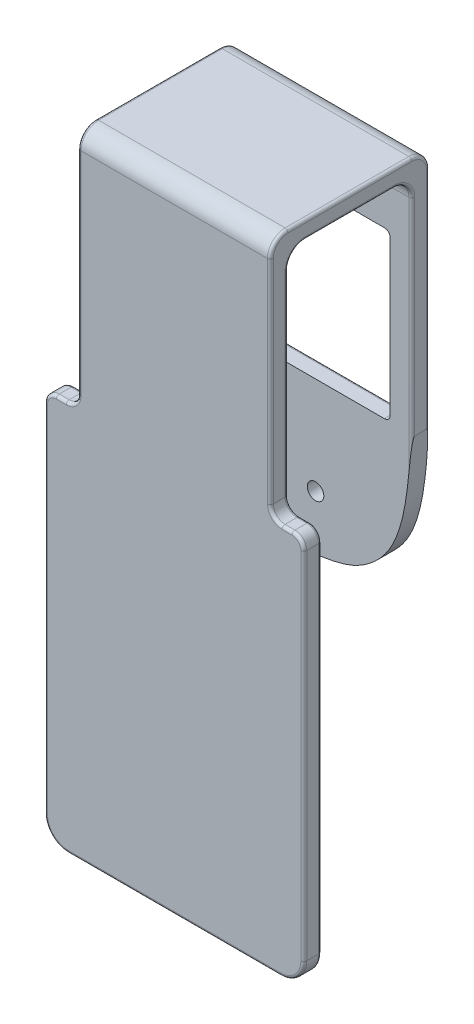
SolidWorks part; units mm, degrees
material "Plastique personnalisé"
ref_plane "Plan de face" through (0, 0, 0) normal (0, 0, 1) x (1, 0, 0)
ref_plane "Plan de dessus" through (0, 0, 0) normal (0, 1, 0) x (1, 0, 0)
ref_plane "Plan de droite" through (0, 0, 0) normal (1, 0, 0) x (0, 0, -1)
sketch "Esquisse1" plane through (0, 0, 0) normal (0, 0, 1) x (1, 0, 0)
  line L0 (19.7337, 104.7956) -> (19.7337, 0) construction
  line L1 (0, 0) -> (44, 0)
  line L2 (0, 0) -> (0, 108)
  line L3 (0, 108) -> (44, 108)
  line L4 (44, 0) -> (44, 108)
  dimension "D1" = 108
  dimension "D2" = 44
extrude "Boss.-Extru.1" add sketch "Esquisse1" along normal blind 3
sketch "Esquisse5" plane through (0, 0, 0) normal (0, 0, -1) x (-1, 0, 0)
  line L0 (-22, 108) -> (-22, 0) construction
  line L1 (-44, 108) -> (0, 108) construction
  line L2 (0, 0) -> (-44, 0) construction
ref_axis "Axe4" through (22, 108, 0) along (0, -1, 0)
fillet "Congé1" radius 4 2 edges at (44, 0, 1.5) (0, 0, 1.5)
ref_plane "Plan1" through (0, 0, -21) normal (0, 0, 1) x (1, 0, 0)
sketch "Esquisse6" plane through (0, 0, -21) normal (0, 0, 1) x (1, 0, 0)
  line L0 (44, 4) -> (44, 108) construction
  line L1 (0, 108) -> (44, 108)
  line L2 (0, 108) -> (0, 41)
  line L3 (0, 41) -> (44, 41)
  line L4 (44, 108) -> (44, 41)
  dimension "D1" = 67
extrude "Boss.-Extru.2" add sketch "Esquisse6" against normal blind 3 separate body
sketch "Esquisse7" plane through (0, 0, -24) normal (0, 0, -1) x (-1, 0, 0)
  circle A0 centre (-21.9933, 50.2726) radius 1.4
  dimension "D1" = 2.8
sketch "Esquisse8" plane through (0, 0, -24) normal (0, 0, -1) x (-1, 0, 0)
  line L1 (-33.6631, 94.8338) -> (-9.59, 94.8338)
  line L2 (-34.6631, 93.8338) -> (-34.6631, 67.778)
  line L3 (-33.6631, 66.778) -> (-9.59, 66.778)
  line L4 (-8.59, 93.8338) -> (-8.59, 67.778)
  arc A0 (-34.6631, 67.778) -> (-33.6631, 66.778) centre (-33.6631, 67.778) ccw
  arc A1 (-9.59, 66.778) -> (-8.59, 67.778) centre (-9.59, 67.778) ccw
  arc A2 (-9.59, 94.8338) -> (-8.59, 93.8338) centre (-9.59, 93.8338) cw
  arc A3 (-33.6631, 94.8338) -> (-34.6631, 93.8338) centre (-33.6631, 93.8338) ccw
  dimension "D1" = 1
extrude "Enlèv. mat.-Extru.1" cut sketch "Esquisse8" against normal blind 3
extrude "Enlèv. mat.-Extru.2" cut sketch "Esquisse7" against normal blind 3
fillet "Congé3" radius 0.5 8 edges at (21.6266, 94.8338, -24) (8.8829, 94.5409, -24) (8.59, 80.8059, -24) (8.8829, 67.0709, -24) (21.6266, 66.778, -24) (34.3702, 67.0709, -24) (34.6631, 80.8059, -24) (34.3702, 94.5409, -24)
sketch "Esquisse9" plane through (0, 0, 0) normal (-1, 0, 0) x (0, 0, 1)
  line L0 (-24, 108) -> (3, 108) construction
  line L1 (-24, 108) -> (-21, 108)
  line L2 (0, 108) -> (3, 108)
  arc A0 (0, 108) -> (-21, 108) centre (-10.5, 108.0295) ccw
  arc A1 (-24, 108) -> (3, 108) centre (-10.5, 108) cw
extrude "Boss.-Extru.3" add sketch "Esquisse9" against normal up to surface (44 mm away) up to face at (44, 74.5, -22.5)
sketch "Esquisse10" plane through (0, 0, -24) normal (0, 0, -1) x (-1, 0, 0)
  line L0 (-5.6774, 95.2299) -> (-5.6774, 121.8398) construction
  line L1 (-5.6774, 66.311) -> (10.9745, 66.311) construction
  line L2 (-22, 108) -> (-22, 125.0168) construction
  line L3 (-5.6774, 128.3291) -> (6.2343, 128.3291)
  line L4 (-5.6774, 128.3291) -> (-5.6774, 66.311)
  line L5 (-5.6774, 66.311) -> (6.2343, 66.311)
  line L6 (6.2343, 128.3291) -> (6.2343, 66.311)
  line L7 (-44, 108) -> (0, 108) construction
  line L8 (-38.3226, 66.311) -> (-50.2343, 66.311)
  line L9 (-50.2343, 128.3291) -> (-50.2343, 66.311)
  line L10 (-38.3226, 128.3291) -> (-50.2343, 128.3291)
  line L11 (-38.3226, 128.3291) -> (-38.3226, 66.311)
extrude "Enlèv. mat.-Extru.3" cut sketch "Esquisse10" against normal through all
sketch "Esquisse11" plane through (0, 0, -24) normal (0, 0, -1) x (-1, 0, 0)
  line L0 (0, 41) -> (-44, 41) construction
  line L1 (-22.0266, 41) -> (-46.9603, 39.1901)
  line L2 (-46.9603, 39.1901) -> (-47.6395, 67.896)
  line L3 (-47.6395, 67.896) -> (-38.3226, 66.311)
  line L4 (-44, 66.311) -> (0, 66.311) construction
  line L5 (-44, 66.311) -> (-38.3226, 66.311) construction
  line L6 (0, 66.311) -> (-22.0266, 66.311) construction
  line L7 (-22.0266, 66.311) -> (-22, 39.0933) construction
  line L8 (3.5832, 67.946) -> (-5.7305, 66.3429)
  line L9 (2.96, 39.2389) -> (3.5832, 67.946)
  line L10 (-21.9771, 41) -> (2.96, 39.2389)
  spline S0 degree 3 poles (-38.3226, 66.311) (-38.0223, 63.3652) (-37.6256, 56.5897) (-35.4159, 47.6559) (-29.3794, 42.6192) (-25.6705, 41.5344) (-22.0266, 41) knots 0 0 0 0 0.286646 0.640364 0.826201 1 1 1 1
  spline S1 degree 3 poles (-5.7305, 66.3429) (-6.0251, 63.3965) (-6.4086, 56.6202) (-8.6009, 47.6821) (-14.6275, 42.6336) (-18.3343, 41.5415) (-21.9771, 41) knots 0 0 0 0 0.286646 0.640364 0.826201 1 1 1 1
extrude "Enlèv. mat.-Extru.4" cut sketch "Esquisse11" against normal blind 3
sketch "Esquisse12" plane through (5.6774, 0, 0) normal (-1, 0, 0) x (0, 0, 1)
  line L0 (-24, 104.3937) -> (3, 104.3937) construction
  line L1 (-24, 108) -> (-24, 66.352) construction
  line L2 (3, 108) -> (3, 66.311) construction
  line L4 (-24, 104.3937) -> (3.7918, 104.3937)
  line L5 (-24, 104.3937) -> (-24, 125.4278)
  line L6 (-24, 125.4278) -> (3.7918, 125.4278)
  line L7 (3.7918, 104.3937) -> (3.7918, 125.4278)
extrude "Enlèv. mat.-Extru.5" cut sketch "Esquisse12" against normal through all
sketch "Esquisse13" plane through (5.6774, 0, 0) normal (-1, 0, 0) x (0, 0, 1)
  line L0 (-24, 104.3937) -> (-21, 104.3937) construction
  line L1 (-24, 104.3937) -> (3, 104.3937)
  line L2 (-24, 104.3937) -> (-24, 107.3937)
  line L3 (-24, 107.3937) -> (3, 107.3937)
  line L4 (3, 104.3937) -> (3, 107.3937)
  dimension "D1" = 3
extrude "Boss.-Extru.4" add sketch "Esquisse13" against normal up to surface (32.6453 mm away) up to face at (38.3226, 85.3524, 1.5)
fillet "Congé4" radius 3 4 edges at (22, 104.3937, 0) (22, 104.3937, -21) (22, 107.3937, -24) (22, 107.3937, 3)
fillet "Congé5" radius 2 4 edges at (38.3226, 66.311, 1.5) (44, 66.311, 1.5) (5.6774, 66.311, 1.5) (0, 66.311, 1.5)
fillet "Congé6" radius 0.5 21 edges at (5.6774, 85.3728, -24) (5.6774, 106.515, -23.1213) (5.6774, 107.3937, -10.5) (5.6774, 106.515, 2.1213) (5.6774, 86.3524, 3) (5.0916, 66.8968, 3) (2.8387, 66.311, 3) (0.5858, 65.7252, 3) (0, 34.1555, 3) (1.1716, 1.1716, 3) (22, 0, 3) (42.8284, 1.1716, 3) (44, 34.1555, 3) (43.4142, 65.7252, 3) (41.1613, 66.311, 3) (38.9084, 66.8968, 3) (38.3226, 86.3524, 3) (38.3226, 106.515, 2.1213) (38.3226, 107.3937, -10.5) (38.3226, 106.515, -23.1213) (38.3226, 85.3524, -24)
fillet "Congé9" radius 0.5 21 edges at (38.3226, 83.8524, -21) (38.3226, 103.515, -20.1213) (38.3226, 104.3937, -10.5) (38.3226, 103.515, -0.8787) (38.3226, 84.8524, 0) (5.6774, 83.8728, -21) (5.6774, 103.515, -20.1213) (5.6774, 104.3937, -10.5) (5.6774, 103.515, -0.8787) (5.6774, 84.8524, 0) (5.0916, 66.8968, 0) (2.8387, 66.311, 0) (0.5858, 65.7252, 0) (0, 34.1555, 0) (1.1716, 1.1716, 0) (22, 0, 0) (42.8284, 1.1716, 0) (44, 34.1555, 0) (43.4142, 65.7252, 0) (41.1613, 66.311, 0) (38.9084, 66.8968, 0)
